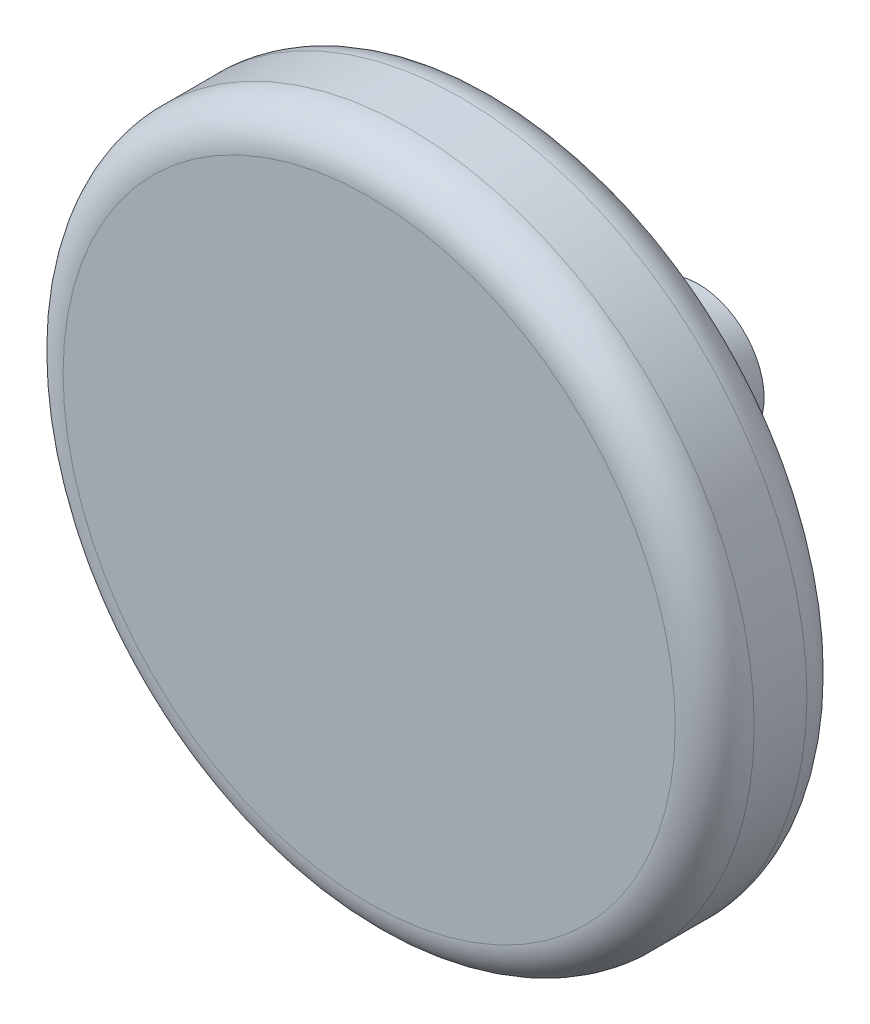
SolidWorks part; units mm, degrees
material "ABS"
ref_plane "Front Plane" through (0, 0, 0) normal (0, 0, 1) x (1, 0, 0)
ref_plane "Top Plane" through (0, 0, 0) normal (0, 1, 0) x (1, 0, 0)
ref_plane "Right Plane" through (0, 0, 0) normal (1, 0, 0) x (0, 0, -1)
sketch "Sketch1" plane through (0, 0, 0) normal (0, 0, 1) x (1, 0, 0)
  circle A0 centre (0, 0) radius 4.2333
  dimension "D1" = 8.4667
extrude "Boss-Extrude1" add sketch "Sketch1" along normal blind 12.7
sketch "Sketch2" plane through (0, 0, 12.7) normal (0, 0, 1) x (1, 0, 0)
  circle A0 centre (0, 0) radius 22.225
  dimension "D1" = 44.45
extrude "Boss-Extrude3" add sketch "Sketch2" along normal blind 8.4667 contours A0
fillet "Fillet1" radius 12.7 1 edges at (4.2333, 0, 12.7)
fillet "Fillet2" radius 2.54 2 edges at (22.225, 0, 12.7) (22.225, 0, 21.1667)
sketch "Sketch5" plane through (0, 0, 0) normal (0, 0, -1) x (-1, 0, 0)
  circle A0 centre (0, 0) radius 1.6256
  dimension "D1" = 3.2512
extrude "Cut-Extrude2" cut sketch "Sketch5" against normal blind 15.621
